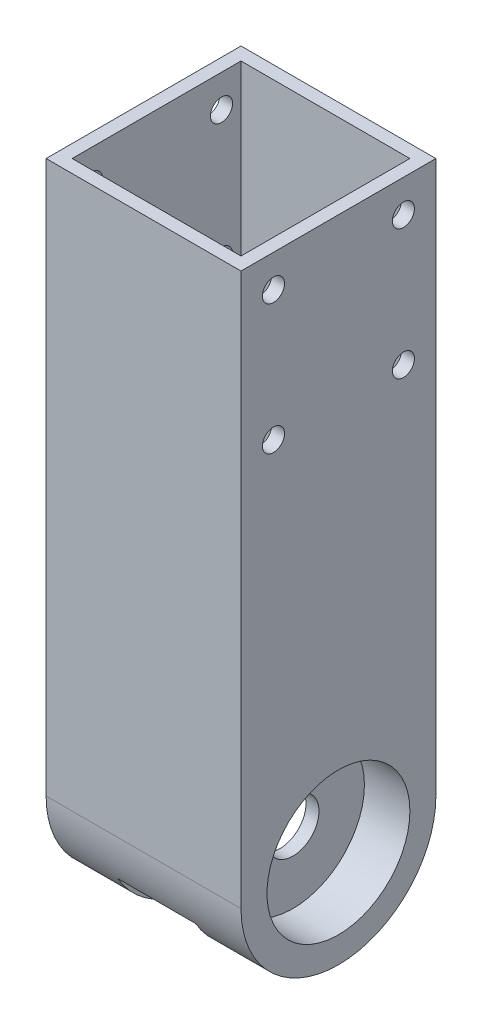
SolidWorks part; units mm, degrees
material "PLA 15%"
ref_plane "Front Plane" through (0, 0, 0) normal (0, 0, 1) x (1, 0, 0)
ref_plane "Top Plane" through (0, 0, 0) normal (0, 1, 0) x (1, 0, 0)
ref_plane "Right Plane" through (0, 0, 0) normal (1, 0, 0) x (0, 0, -1)
sketch "Sketch1" plane through (0, 0, 0) normal (0, 1, 0) x (1, 0, 0)
  line L1 (-15, -15) -> (15, -15)
  line L2 (-15, -15) -> (-15, 15)
  line L3 (-15, 15) -> (15, 15)
  line L4 (15, -15) -> (15, 15)
  line L5 (-15, -15) -> (15, 15) construction
  line L6 (-15, 15) -> (15, -15) construction
  line L11 (-6, -6) -> (6, 6) construction
  line L12 (-6, 6) -> (6, -6) construction
  line L13 (-6, -13) -> (6, -13)
  line L14 (-6, -13) -> (-6, 13)
  line L15 (-6, 13) -> (6, 13)
  line L16 (6, -13) -> (6, 13)
  line L17 (-6, -13) -> (6, 13) construction
  line L18 (-6, 13) -> (6, -13) construction
  point P0 (0, 0)
  point P6 (0, 0)
  point P11 (0, 0)
  dimension "D1" = 30
  dimension "D2" = 30
  dimension "D3" = 9
  dimension "D4" = 2
extrude "Boss-Extrude2" add sketch "Sketch1" along normal blind 100
sketch "Sketch2" plane through (15, 0, 0) normal (1, 0, 0) x (0, 0, -1)
  line L0 (-15, 95) -> (15, 95)
  line L1 (-15, 100) -> (-15, 0) construction
  line L2 (15, 100) -> (15, 0) construction
  line L3 (-15, 100) -> (15, 100) construction
  line L4 (-15, 100) -> (-15, 70) construction
  line L5 (-15, 70) -> (15, 70) construction
  line L6 (-15, 70) -> (15, 70)
  line L8 (-12, 93) -> (-8, 93)
  line L9 (-12, 93) -> (-12, 97)
  line L10 (-12, 97) -> (-8, 97)
  line L11 (-8, 93) -> (-8, 97)
  line L12 (-12, 93) -> (-8, 97) construction
  line L13 (-12, 97) -> (-8, 93) construction
  line L14 (12, 97) -> (8, 97)
  line L15 (12, 97) -> (12, 93)
  line L16 (12, 93) -> (8, 93)
  line L17 (8, 97) -> (8, 93)
  line L18 (12, 97) -> (8, 93) construction
  line L19 (12, 93) -> (8, 97) construction
  line L20 (-12, 73) -> (-8, 73)
  line L21 (-12, 73) -> (-12, 77)
  line L22 (-12, 77) -> (-8, 77)
  line L23 (-8, 73) -> (-8, 77)
  line L24 (-12, 73) -> (-8, 77) construction
  line L25 (-12, 77) -> (-8, 73) construction
  line L26 (8, 73) -> (12, 73)
  line L27 (8, 73) -> (8, 77)
  line L28 (8, 77) -> (12, 77)
  line L29 (12, 73) -> (12, 77)
  line L30 (8, 73) -> (12, 77) construction
  line L31 (8, 77) -> (12, 73) construction
  circle A0 centre (-10, 95) radius 2
  circle A1 centre (10, 95) radius 2
  circle A4 centre (-10, 75) radius 2
  circle A5 centre (10, 75) radius 2
  dimension "D2" = 4
  dimension "D4" = 4
  dimension "D7" = 5
  dimension "D8" = 4
  dimension "D9" = 5
  dimension "D11" = 4
  dimension "D13" = 4
  dimension "D1" = 5
  dimension "D3" = 5
  dimension "D5" = 5
  dimension "D6" = 30
  dimension "D10" = 5
  dimension "D12" = 5
  dimension "D14" = 4
  dimension "D15" = 4
  dimension "D16" = 4
  dimension "D17" = 4
  dimension "D18" = 4
sketch "Sketch3" plane through (0, 100, 0) normal (0, 1, 0) x (1, 0, 0)
  line L0 (-6, 13) -> (-13, 13)
  line L1 (-15, 15) -> (-15, -15) construction
  line L2 (-13, 13) -> (-13, -13)
  line L7 (-6, -13) -> (-13, -13)
  line L8 (-6, 13) -> (-6, -13)
  line L9 (15, -15) -> (15, 15) construction
  line L10 (6, 13) -> (13, 13)
  line L11 (6, 13) -> (6, -13)
  line L12 (6, -13) -> (13, -13)
  line L13 (13, 13) -> (13, -13)
  dimension "D1" = 2
  dimension "D2" = 2
extrude "Cut-Extrude2" cut sketch "Sketch3" against normal blind 70
fillet "Fillet1" radius 15 2 edges at (0, 0, -15) (0, 0, 15)
sketch "Sketch5" plane through (15, 0, 0) normal (1, 0, 0) x (0, 0, -1)
  circle A0 centre (0, 15) radius 4
  dimension "D1" = 8
extrude "Cut-Extrude3" cut sketch "Sketch5" against normal blind 50
sketch "Sketch6" plane through (15, 0, 0) normal (1, 0, 0) x (0, 0, -1)
  circle A0 centre (0, 15) radius 11
  dimension "D1" = 22
extrude "Cut-Extrude4" cut sketch "Sketch6" against normal blind 7
sketch "Sketch7" plane through (-15, 0, 0) normal (-1, 0, 0) x (0, 0, 1)
  circle A0 centre (0, 15) radius 11
  dimension "D1" = 22
extrude "Cut-Extrude5" cut sketch "Sketch7" against normal blind 7
sketch "Sketch8" plane through (15, 0, 0) normal (1, 0, 0) x (0, 0, -1)
  line L3 (10, 75) -> (-10, 75) construction
  line L6 (10, 15) -> (10, 95)
  line L7 (10, 95) -> (-10, 95)
  line L8 (-10, 95) -> (-10, 15)
  line L9 (10, 75) -> (10, 95) construction
  line L10 (10, 95) -> (-10, 95) construction
  line L11 (-10, 95) -> (-10, 75) construction
  arc A4 (-10, 15) -> (0, 5) centre (0, 15) ccw
  arc A5 (0, 5) -> (10, 15) centre (0, 15) ccw
  point P13 (-10, 75)
  point P18 (10, 75)
  point P19 (10, 95)
  point P20 (-10, 95)
  dimension "D1" = 5
hole_wizard "M3 Clearance Hole1" positions "Sketch8" profile "Sketch9" hole size "M3" standard "ANSI Metric" end condition through all
sketch "Sketch9" plane through (15, 95, 10) normal (0, 1, 0) x (0, 0, -1)
  line L0 (0, 0) -> (0, 30)
  line L1 (0, 30) -> (1.7, 30)
  line L2 (1.7, 30) -> (1.7, 0)
  line L5 (1.7, 0) -> (0, 0)
  line L11 (0, -6.35) -> (0, 107.95) construction
  dimension "Thru Hole Dia." = 3.4
  dimension "Thru Hole Depth" = 30
